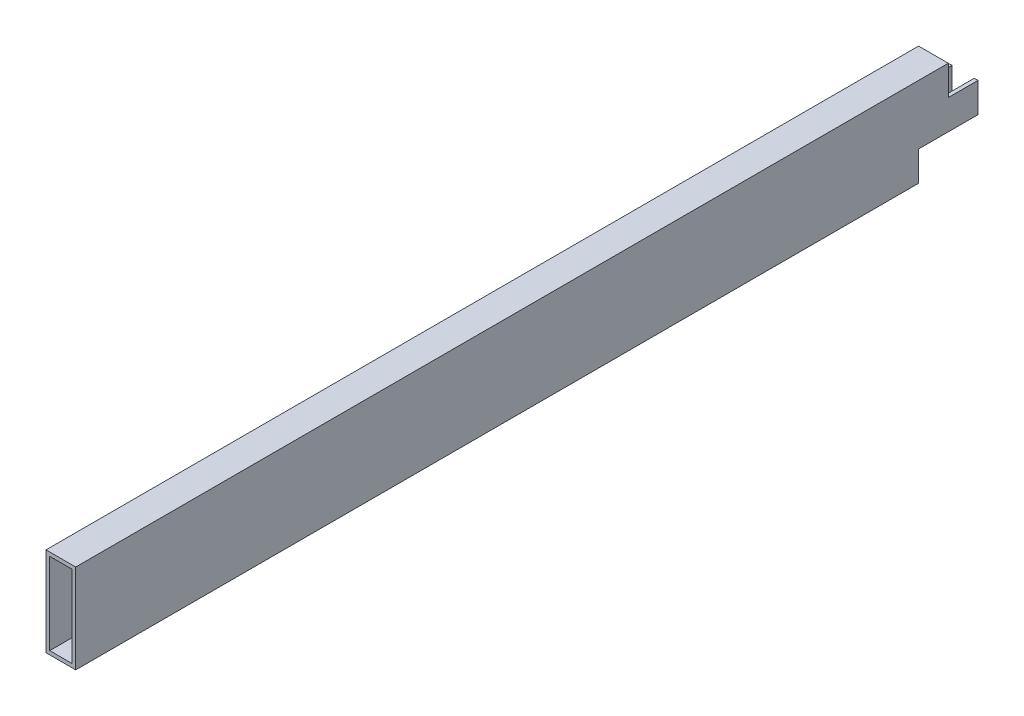
SolidWorks part; units mm, degrees
ref_plane "Front Plane" through (0, 0, 0) normal (0, 0, 1) x (1, 0, 0)
ref_plane "Top Plane" through (0, 0, 0) normal (0, 1, 0) x (1, 0, 0)
ref_plane "Right Plane" through (0, 0, 0) normal (1, 0, 0) x (0, 0, -1)
sketch "Sketch1" plane through (0, 0, 0) normal (0, 0, 1) x (1, 0, 0)
  line L1 (-12.7, -38.1) -> (12.7, -38.1)
  line L2 (-12.7, -38.1) -> (-12.7, 38.1)
  line L3 (-12.7, 38.1) -> (12.7, 38.1)
  line L4 (12.7, -38.1) -> (12.7, 38.1)
  line L5 (-12.7, -38.1) -> (12.7, 38.1) construction
  line L6 (-12.7, 38.1) -> (12.7, -38.1) construction
  point P0 (0, 0)
  dimension "D1" = 25.4
  dimension "D2" = 76.2
extrude "Boss-Extrude1" add sketch "Sketch1" along normal mid plane 771.398
shell "Shell1" thickness 3.175 removed face at (0, 0, -385.699) removed face at (0, 0, 385.699)
sketch "Sketch2" plane through (12.7, 0, 0) normal (1, 0, 0) x (0, 0, -1)
  line L1 (385.699, -38.1) -> (334.899, -38.1)
  line L2 (385.699, -38.1) -> (385.699, -12.7)
  line L3 (385.699, -12.7) -> (334.899, -12.7)
  line L4 (334.899, -38.1) -> (334.899, -12.7)
  dimension "D1" = 25.4
  dimension "D2" = 50.8
extrude "Cut-Extrude1" cut sketch "Sketch2" against normal through all
sketch "Sketch3" plane through (12.7, 0, 0) normal (1, 0, 0) x (0, 0, -1)
  line L1 (385.699, 38.1) -> (360.299, 38.1)
  line L2 (385.699, 38.1) -> (385.699, 12.7)
  line L3 (385.699, 12.7) -> (360.299, 12.7)
  line L4 (360.299, 38.1) -> (360.299, 12.7)
  dimension "D1" = 25.4
extrude "Cut-Extrude2" cut sketch "Sketch3" against normal through all
